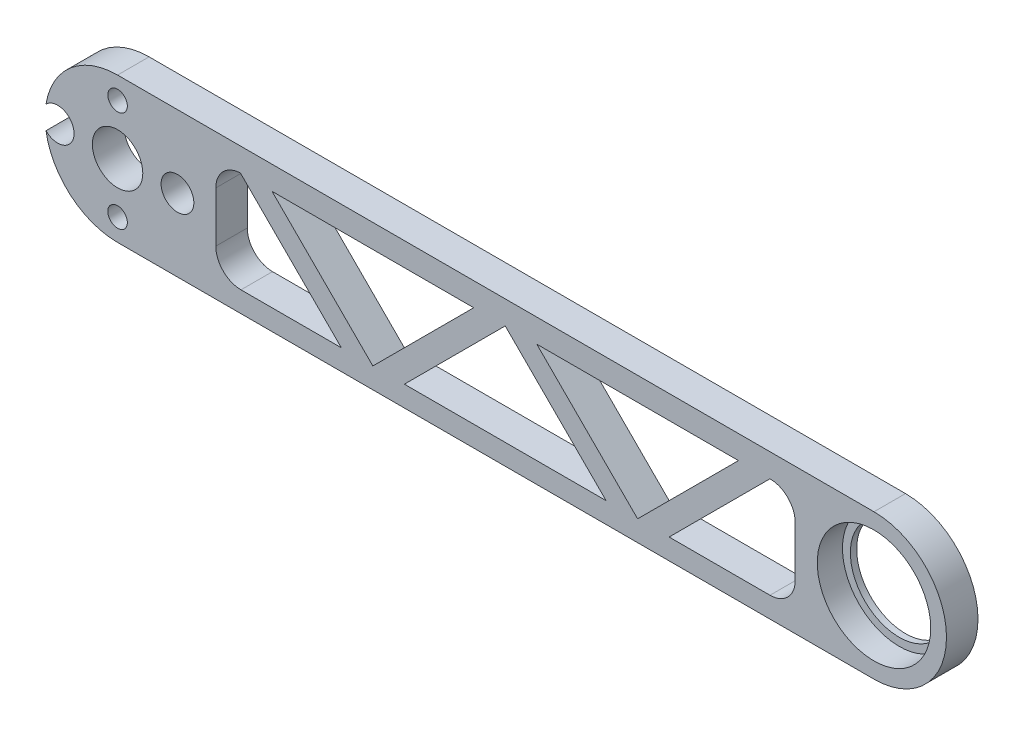
SolidWorks part; units mm, degrees
note: The reader was unsure of these and kept them because the rebuilt part matched: shared geometry of "Sketch8<3>", "Sketch8<4>".
ref_plane "前视基准面" through (0, 0, 0) normal (0, 0, 1) x (1, 0, 0)
ref_plane "上视基准面" through (0, 0, 0) normal (0, 1, 0) x (1, 0, 0)
ref_plane "右视基准面" through (0, 0, 0) normal (1, 0, 0) x (0, 0, -1)
other "Configuration Table"
sketch "Sketch1" plane through (0, 0, 0) normal (0, 0, 1) x (1, 0, 0)
  line L0 (0, 0) -> (120, 0) construction
  line L1 (0, 11.5) -> (120, 11.5)
  line L2 (0, -11.5) -> (120, -11.5)
  arc A0 (0, 11.5) -> (0, -11.5) centre (0, 0) ccw
  arc A1 (120, -11.5) -> (120, 11.5) centre (120, 0) ccw
  point P3 (60, 0)
extrude "Boss-Extrude1" add sketch "Sketch1" against normal blind 5
sketch "Sketch2" plane through (0, 0, 0) normal (0, 0, 1) x (1, 0, 0)
  circle A0 centre (120, 0) radius 9
extrude "Cut-Extrude1" cut sketch "Sketch2" against normal blind 4 contours A0
sketch "Sketch3" plane through (0, 0, 0) normal (0, 0, 1) x (1, 0, 0)
  circle A0 centre (120, 0) radius 7.75
extrude "Cut-Extrude2" cut sketch "Sketch3" against normal blind 15 contours A0
sketch "Sketch4" plane through (0, 0, 0) normal (0, 0, 1) x (1, 0, 0)
  circle A0 centre (0, 0) radius 4
extrude "Cut-Extrude3" cut sketch "Sketch4" against normal blind 15 contours A0
sketch "Sketch5" plane through (0, 0, 0) normal (0, 0, 1) x (1, 0, 0)
  circle A0 centre (0, 8) radius 1.55
  circle A1 centre (0, -8) radius 1.55
  dimension "D1" = 16
  dimension "D2" = 8
sketch "Sketch6" plane through (0, 0, 0) normal (0, 0, 1) x (1, 0, 0)
  circle A0 centre (-9.5, 0) radius 2.6
  circle A1 centre (9.5, 0) radius 2.6
  dimension "D1" = 19
  dimension "D2" = 9.5
extrude "Cut-Extrude4" cut sketch "Sketch5" against normal blind 15
extrude "Cut-Extrude5" cut sketch "Sketch6" against normal blind 15
sketch "Sketch8" plane through (0, 0, 0) normal (0, 0, 1) x (1, 0, 0)
  line L1 (103.5, 7.7797) -> (19.5, 7.7797)
  line L2 (107.5, 3.7797) -> (107.5, -4.2203)
  line L3 (103.5, -8.2203) -> (19.5781, -8.2203)
  line L4 (15.5781, 3.7805) -> (15.5781, -4.2203)
  line L14 (103.5, 7.7797) -> (98.5, 7.7797)
  line L15 (103.5, 7.7797) -> (87.5, -8.2203)
  line L16 (98.5, 7.7797) -> (82.5, -8.2203)
  line L17 (87.5, -8.2203) -> (82.5, -8.2203)
  line L22 (82.5, -8.2203) -> (77.5, -8.2203)
  line L23 (82.5, -8.2203) -> (66.5, 7.7797)
  line L24 (77.5, -8.2203) -> (61.5, 7.7797)
  line L25 (66.5, 7.7797) -> (61.5, 7.7797)
  line L26 (61.5, 7.7797) -> (56.5, 7.7797)
  line L27 (61.5, 7.7797) -> (45.5, -8.2203)
  line L28 (56.5, 7.7797) -> (40.5, -8.2203)
  line L29 (45.5, -8.2203) -> (40.5, -8.2203)
  line L30 (40.5, -8.2203) -> (35.5, -8.2203)
  line L31 (40.5, -8.2203) -> (24.5, 7.7797)
  line L32 (35.5, -8.2203) -> (19.5, 7.7797)
  line L33 (24.5, 7.7797) -> (19.5, 7.7797)
  circle A0 centre (9.5, 0) radius 2.6 construction
  arc A1 (19.5781, -8.2203) -> (15.5781, -4.2203) centre (19.5781, -4.2203) cw
  arc A2 (19.5, 7.7797) -> (15.5781, 3.7805) centre (19.5781, 3.7805) ccw
  arc A3 (107.5, -4.2203) -> (103.5, -8.2203) centre (103.5, -4.2203) cw
  arc A4 (103.5, 7.7797) -> (107.5, 3.7797) centre (103.5, 3.7797) cw
  point P4 (0, 0)
  point P5 (0, 0)
  point P11 (15.5781, 7.7797)
  point P14 (107.5, -8.2203)
  point P17 (107.5, 7.7797)
  point P19 (103.29, 7.5621)
  dimension "D3" = 42
  dimension "D5" = 4
  dimension "D2" = 84
  dimension "D4" = 5
  dimension "D6" = 10
  dimension "D7" = 42
  dimension "D8" = 21
  dimension "D10" = 5
  dimension "D12" = 5
  dimension "D14" = 5
extrude "Cut-Extrude7" cut sketch "Sketch8" against normal blind 15
extrude "Cut-Extrude8" cut sketch "Sketch8<3>" against normal blind 10 contours L31 L28 L1 | L24 L27 L3
sketch "Sketch8<3>" plane through (0, 0, 0) normal (0, 0, 1) x (1, 0, 0) same geometry as "Sketch8"
sketch "Sketch9" plane through (0, 0, -5) normal (0, 0, -1) x (-1, 0, 0)
  circle A0 centre (0, 8) radius 2.75
  circle A1 centre (0, -8) radius 2.75
extrude "Cut-Extrude10" cut sketch "Sketch9" against normal blind 2.8
extrude "Boss-Extrude2" add sketch "Sketch8<4>" against normal blind 5 contours L24 L3 L23 L1 | L1 L16 L3 L15
sketch "Sketch8<4>" plane through (0, 0, 0) normal (0, 0, 1) x (1, 0, 0) same geometry as "Sketch8"
